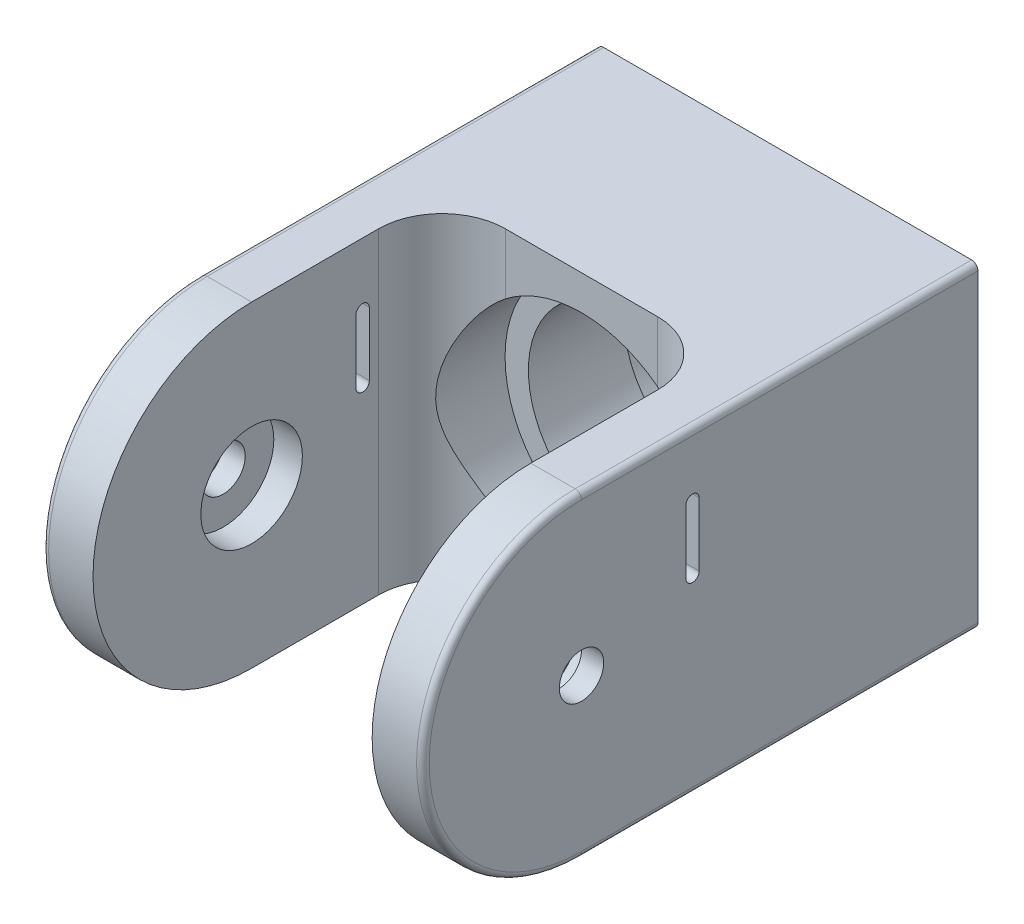
SolidWorks part; units mm, degrees
ref_plane "Front Plane" through (0, 0, 0) normal (0, 0, 1) x (1, 0, 0)
ref_plane "Top Plane" through (0, 0, 0) normal (0, 1, 0) x (1, 0, 0)
ref_plane "Right Plane" through (0, 0, 0) normal (1, 0, 0) x (0, 0, -1)
sketch "Sketch1" plane through (0, 0, 0) normal (0, 0, 1) x (1, 0, 0)
  circle A2 centre (0, 0) radius 31.75
  circle A4 centre (0, 0) radius 39.1
  circle A5 centre (0, 0) radius 38.1 construction
  dimension "D1" = 1
  dimension "D2" = 63.5
extrude "Centre Hole for L2" add sketch "Sketch1" along normal blind 30 contours A4 | A2
sketch "Sketch2" plane through (0, 0, 30) normal (0, 0, 1) x (1, 0, 0)
  line L0 (0, 48.4974) -> (0, 0) construction
  line L5 (-60, 50) -> (-60, -50)
  line L12 (0, 0) -> (72.986, 0) construction
  line L16 (-60, 50) -> (60, 50)
  line L17 (60, 50) -> (60, -50)
  line L18 (-60, -50) -> (60, -50)
  circle A2 centre (0, 0) radius 39.1
  circle A3 centre (0, 0) radius 39.1 construction
  point P13 (0, 50)
  dimension "D1" = 60
  dimension "D2" = 100
extrude "Main Structure" add sketch "Sketch2" along normal blind 75 and the other way blind 50 separate body contours L5 L18 L17 L16 A2
sketch "Sketch3" plane through (-60, 0, 0) normal (-1, 0, 0) x (0, 0, 1)
  line L0 (105, 50) -> (105, -50) construction
  line L1 (105, 50) -> (105, -50)
  line L2 (-20, 50) -> (105, 50) construction
  arc A0 (105, 50) -> (105, -50) centre (105, 0) cw
extrude "Bearing Curve" add sketch "Sketch3" against normal blind 16 contours A0 L1
mirror "Upright Mirror" about plane through (0, 0, 0) normal (1, 0, 0) of "Bearing Curve"
sketch "Sketch6" plane through (-60, 0, 0) normal (-1, 0, 0) x (0, 0, 1)
  circle A0 centre (105, 0) radius 7
  dimension "D1" = 14
extrude "Shaft Hole" cut sketch "Sketch6" against normal up to surface (16 mm away) up to face at (-44, 0, 130)
sketch "Sketch4" plane through (0, 50, 0) normal (0, 1, 0) x (1, 0, 0)
  line L0 (0, -110) -> (0, 20) construction
  line L1 (-44, -105) -> (44, -105) construction
  line L2 (-60, 20) -> (60, 20) construction
  line L3 (-44, -105) -> (-44, -65)
  line L4 (-24, -45) -> (24, -45)
  line L5 (-44, -105) -> (44, -105)
  line L6 (44, -105) -> (44, -65)
  arc A0 (-44, -65) -> (-24, -45) centre (-24, -65) cw
  arc A1 (44, -65) -> (24, -45) centre (24, -65) ccw
  point P17 (0, -105)
  point P20 (0, -45)
  dimension "D2" = 20
  dimension "D1" = 65
extrude "Wrist Cutout" cut sketch "Sketch4" against normal through all
sketch "Sketch9" plane through (-44, 0, 0) normal (1, 0, 0) x (0, 0, -1)
  circle A0 centre (-105, 0) radius 16
  dimension "D1" = 32
extrude "Bearing" cut sketch "Sketch9" against normal blind 9
mirror "Bearing Mirror" about plane through (0, 0, 0) normal (1, 0, 0) of "Bearing", "Shaft Hole"
fillet "Fillet1" radius 2 6 edges at (-60, 50, 42.5) (-60, -50, 42.5) (60, -50, 42.5) (60, 50, 42.5) (-60, 0, 155) (60, 0, 155)
sketch "Sketch14" plane through (-60, 0, 0) normal (-1, 0, 0) x (0, 0, 1)
  line L0 (70, 30) -> (70, 10) construction
  line L1 (72.1, 30) -> (72.1, 10)
  line L2 (67.9, 30) -> (67.9, 10)
  arc A0 (72.1, 30) -> (67.9, 30) centre (70, 30) ccw
  arc A1 (67.9, 10) -> (72.1, 10) centre (70, 10) ccw
  point P2 (70, 20)
  dimension "D1" = 4.2
  dimension "D2" = 20
  dimension "D3" = 10
  dimension "D4" = 70
extrude "Tensioner Slot" cut sketch "Sketch14" against normal up to surface (16 mm away) up to face at (-44, 0, 89)
mirror "Mirror9" about plane through (0, 0, 0) normal (1, 0, 0) of "Tensioner Slot"
